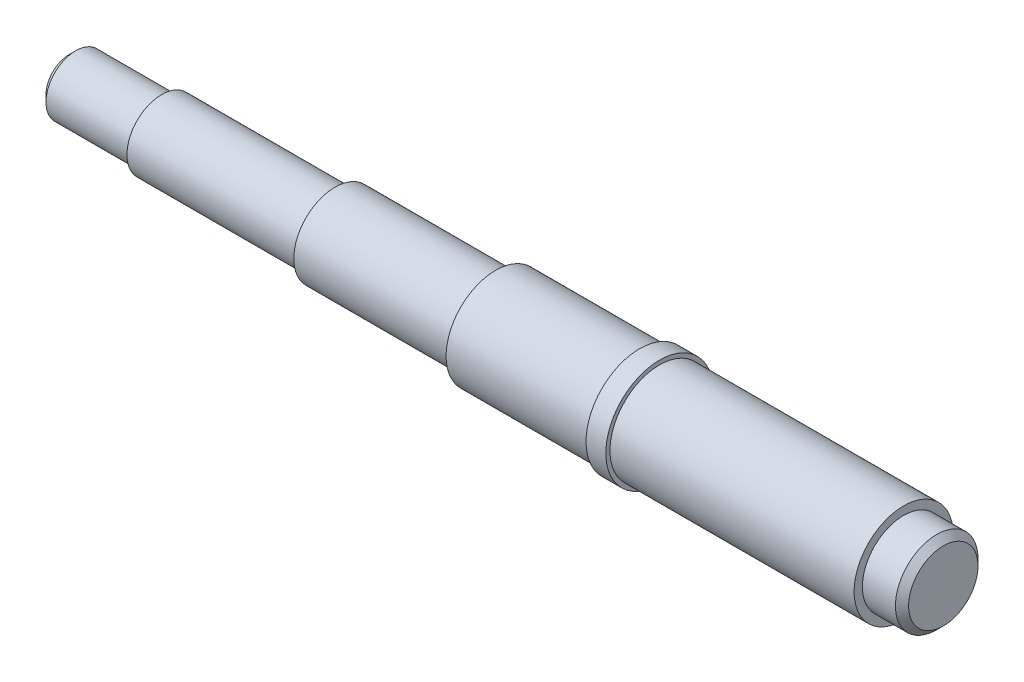
SolidWorks part; units mm, degrees
ref_plane "前视基准面" through (0, 0, 0) normal (0, 0, 1) x (1, 0, 0)
ref_plane "上视基准面" through (0, 0, 0) normal (0, 1, 0) x (1, 0, 0)
ref_plane "右视基准面" through (0, 0, 0) normal (1, 0, 0) x (0, 0, -1)
sketch "草图1" plane through (0, 0, 0) normal (0, 0, 1) x (1, 0, 0)
  line L0 (0, 0) -> (0, 9)
  line L1 (0, 9) -> (28, 9)
  line L2 (28, 9) -> (28, 10.5)
  line L3 (28, 10.5) -> (80.5, 10.5)
  line L4 (80.5, 10.5) -> (80.5, 12.5)
  line L5 (80.5, 12.5) -> (129.1, 12.5)
  line L6 (129.1, 12.5) -> (129.1, 15)
  line L7 (129.1, 15) -> (172.7, 15)
  line L8 (172.7, 15) -> (172.7, 16.25)
  line L9 (172.7, 16.25) -> (178.7, 16.25)
  line L10 (178.7, 16.25) -> (178.7, 15)
  line L11 (178.7, 15) -> (252.6, 15)
  line L12 (252.6, 15) -> (252.6, 12.5)
  line L13 (252.6, 12.5) -> (264.6, 12.5)
  line L14 (264.6, 12.5) -> (264.6, 0)
  line L15 (264.6, 0) -> (0, 0)
  dimension "D1" = 9
  dimension "D2" = 10.5
  dimension "D3" = 12.5
  dimension "D4" = 15
  dimension "D5" = 15
  dimension "D6" = 12.5
  dimension "D7" = 28
  dimension "D8" = 52.5
  dimension "D9" = 48.6
  dimension "D10" = 43.6
  dimension "D11" = 6
  dimension "D12" = 16.25
  dimension "D13" = 12
  dimension "D14" = 73.9
revolve "旋转1" add sketch "草图1" angle 360 about L15
chamfer "倒角1" distance 2 angle 45 2 edges at (264.6, 0, -12.5) (0, 0, -9)
sketch "草图2" plane through (0, 0, 0) normal (0, 0, 1) x (1, 0, 0)
  line L0 (129.1, 0) -> (172.7, 0)
  line L1 (129.1, 15) -> (129.1, -15) construction
  line L2 (172.7, 15) -> (172.7, -15) construction
  line L4 (141.9, 4) -> (159.9, 4)
  line L5 (141.9, 4) -> (141.9, -4)
  line L6 (141.9, -4) -> (159.9, -4)
  line L7 (159.9, 4) -> (159.9, -4)
  line L8 (150.9, -4) -> (150.9, 4) construction
  line L9 (141.9, 0) -> (159.9, 0) construction
  point P6 (150.9, 0)
  dimension "D1" = 8
  dimension "D2" = 18
extrude "切除-拉伸1" cut sketch "草图2" against normal blind 28 from offset 11.5 contours L7 L0 L5 L6 | L7 L4 L5 L0 region at (150.9, 2, 0) region at (150.9, -2, 0) offset against normal yes
